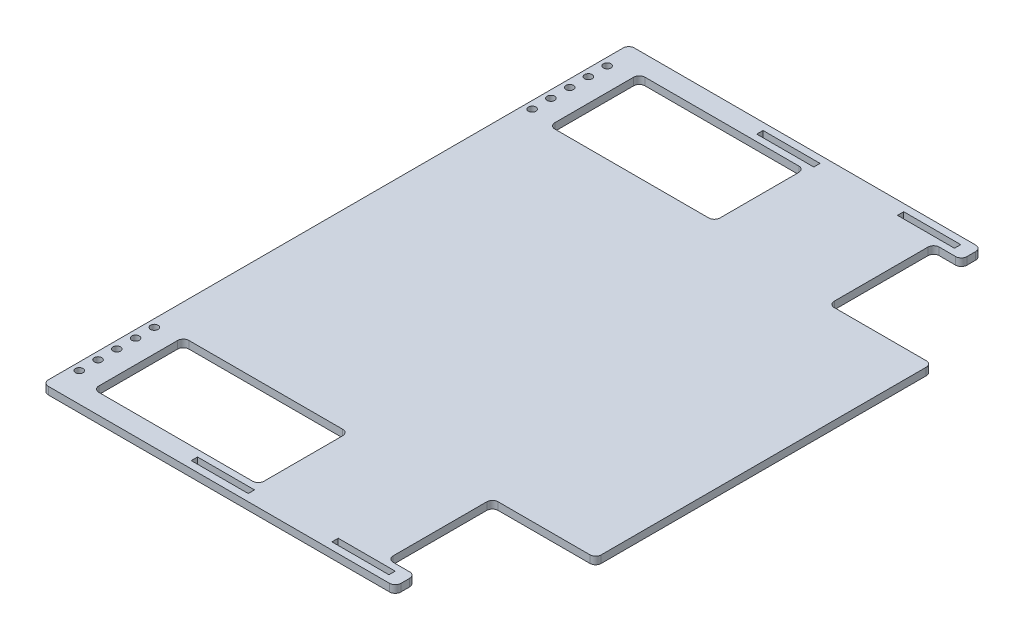
SolidWorks part; units mm, degrees
ref_plane "Front Plane" through (0, 0, 0) normal (0, 0, 1) x (1, 0, 0)
ref_plane "Top Plane" through (0, 0, 0) normal (0, 1, 0) x (1, 0, 0)
ref_plane "Right Plane" through (0, 0, 0) normal (1, 0, 0) x (0, 0, -1)
sketch "Sketch1" plane through (0, 0, 0) normal (0, 1, 0) x (1, 0, 0)
  line L0 (-100, 156.215) -> (-100, -156.215)
  line L1 (-100, 156.215) -> (87.95, 156.215)
  line L2 (-100, -156.215) -> (87.95, -156.215)
  line L3 (87.95, 156.215) -> (87.95, 145.555)
  line L4 (87.95, 145.555) -> (73.17, 145.555)
  line L5 (73.17, 145.555) -> (73.17, 89.625)
  line L6 (-215.5487, 0) -> (286.775, 0) construction
  line L7 (73.17, 89.625) -> (128.17, 89.625)
  line L8 (128.17, 89.625) -> (128.17, -89.625)
  line L9 (73.17, -89.625) -> (128.17, -89.625)
  line L10 (73.17, -145.555) -> (73.17, -89.625)
  line L11 (87.95, -145.555) -> (73.17, -145.555)
  line L12 (87.95, -156.215) -> (87.95, -145.555)
  line L13 (50.39, 152.415) -> (80.79, 152.415)
  line L14 (-83.71, 145.555) -> (4.29, 145.555)
  line L15 (-83.71, 145.555) -> (-83.71, 97.555)
  line L16 (-83.71, 97.555) -> (4.29, 97.555)
  line L17 (4.29, 145.555) -> (4.29, 97.555)
  line L18 (-24.61, 152.415) -> (5.79, 152.415)
  line L19 (-24.61, 152.415) -> (-24.61, 149.065)
  line L20 (-24.61, 149.065) -> (5.79, 149.065)
  line L21 (5.79, 152.415) -> (5.79, 149.065)
  line L22 (50.39, 152.415) -> (50.39, 149.065)
  line L23 (50.39, 149.065) -> (80.79, 149.065)
  line L24 (80.79, 152.415) -> (80.79, 149.065)
  line L25 (50.39, -152.415) -> (50.39, -149.065)
  line L26 (50.39, -149.065) -> (80.79, -149.065)
  line L27 (80.79, -152.415) -> (80.79, -149.065)
  line L28 (50.39, -152.415) -> (80.79, -152.415)
  line L29 (-24.61, -149.065) -> (5.79, -149.065)
  line L30 (5.79, -152.415) -> (5.79, -149.065)
  line L31 (-24.61, -152.415) -> (5.79, -152.415)
  line L32 (-24.61, -152.415) -> (-24.61, -149.065)
  line L33 (-83.71, -97.555) -> (4.29, -97.555)
  line L34 (4.29, -145.555) -> (4.29, -97.555)
  line L35 (-83.71, -145.555) -> (4.29, -145.555)
  line L36 (-83.71, -145.555) -> (-83.71, -97.555)
  circle A0 centre (-96, 140.715) radius 2
  circle A1 centre (-96, 130.715) radius 2
  circle A2 centre (-96, 120.715) radius 2
  circle A3 centre (-96, 110.715) radius 2
  circle A4 centre (-96, 100.715) radius 2
  circle A5 centre (-96, -100.715) radius 2
  circle A6 centre (-96, -110.715) radius 2
  circle A7 centre (-96, -120.715) radius 2
  circle A8 centre (-96, -130.715) radius 2
  circle A9 centre (-96, -140.715) radius 2
  point P13 (128.17, 0)
  dimension "D11" = 4
  dimension "D13" = 4
  dimension "D25" = 4
  dimension "D1" = 312.43
  dimension "D2" = 187.95
  dimension "D3" = 228.17
  dimension "D4" = 14.78
  dimension "D5" = 55.93
  dimension "D6" = 10.66
  dimension "D7" = 48
  dimension "D8" = 88
  dimension "D9" = 10.66
  dimension "D10" = 16.29
  dimension "D12" = 15.5
  dimension "D15" = 30.4
  dimension "D16" = 3.35
  dimension "D17" = 75.39
  dimension "D18" = 3.8
  dimension "D19" = 3.8
  dimension "D20" = 44.6
  dimension "D21" = 3.35
  dimension "D22" = 100
  dimension "D23" = 30.4
  dimension "D24" = 10
  dimension "D14" = 5
extrude "Boss-Extrude1" add sketch "Sketch1" along normal blind 4
fillet "Fillet1" radius 3 20 edges at (-100, 2, 156.215) (4.29, 2, 97.555) (4.29, 2, 145.555) (-83.71, 2, 145.555) (-83.71, 2, 97.555) (87.95, 2, 156.215) (87.95, 2, 145.555) (73.17, 2, 145.555) (73.17, 2, 89.625) (128.17, 2, 89.625) (-100, 2, -156.215) (4.29, 2, -97.555) (4.29, 2, -145.555) (-83.71, 2, -145.555) (-83.71, 2, -97.555) (128.17, 2, -89.625) (73.17, 2, -89.625) (73.17, 2, -145.555) (87.95, 2, -156.215) (87.95, 2, -145.555)
